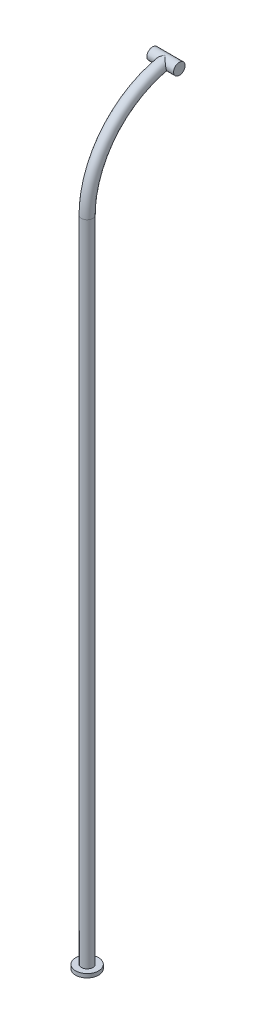
SolidWorks part; units mm, degrees
material "Nylon 101"
ref_plane "Front Plane" through (0, 0, 0) normal (0, 0, 1) x (1, 0, 0)
ref_plane "Top Plane" through (0, 0, 0) normal (0, 1, 0) x (1, 0, 0)
ref_plane "Right Plane" through (0, 0, 0) normal (1, 0, 0) x (0, 0, -1)
sketch "Sketch1" plane through (0, 0, 0) normal (0, 1, 0) x (1, 0, 0)
  circle A0 centre (0, 0) radius 1.5
extrude "Boss-Extrude1" add sketch "Sketch1" along normal blind 170
sketch "Sketch4" plane through (0, 0, 0) normal (0, -1, 0) x (1, 0, 0)
  circle A0 centre (0, 0) radius 3
extrude "Boss-Extrude4" add sketch "Sketch4" along normal blind 1
sketch "Sketch7" plane through (0, 170, 0) normal (0, 1, 0) x (1, 0, 0)
  line L0 (0, 0) -> (0, 44.3626) construction
  line L1 (0, 44.3626) -> (0, 25) construction
  line L2 (0, 25) -> (-42.5101, 25) construction
  line L3 (-42.5101, 25) -> (39.1951, 25) construction
  circle A0 centre (0, 0) radius 1.5
  dimension "D1" = 25
revolve "Revolve1" add sketch "Sketch7" angle 80 about L3 reverse direction yes
sketch "Sketch8" plane through (0, 0, 0) normal (1, 0, 0) x (0, 0, -1)
  line L0 (20.9193, 193.143) -> (20.3983, 196.0974) construction
  circle A0 centre (20.6588, 194.6202) radius 1.5
extrude "Boss-Extrude5" add sketch "Sketch8" along normal blind 3.5 and the other way blind 3.5
equation "\"4.5.00mm\"=10"
